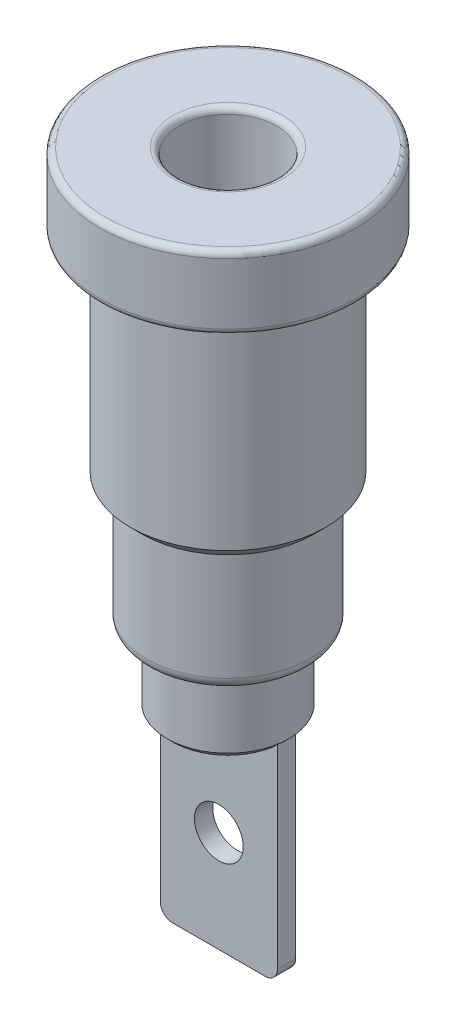
SolidWorks part; units mm, degrees
ref_plane "Front Plane" through (0, 0, 0) normal (0, 0, 1) x (1, 0, 0)
ref_plane "Top Plane" through (0, 0, 0) normal (0, 1, 0) x (1, 0, 0)
ref_plane "Right Plane" through (0, 0, 0) normal (1, 0, 0) x (0, 0, -1)
sketch "Sketch1" plane through (0, 0, 0) normal (0, 0, 1) x (1, 0, 0)
  line L0 (-2, 0) -> (-5.25, 0)
  line L1 (-5.25, 0) -> (-5.25, -3)
  line L2 (-5.25, -3) -> (-4, -3)
  line L5 (-4, -3) -> (-4, -12)
  line L6 (-4, -12) -> (-3.34, -12)
  line L7 (-3.34, -12) -> (-3.34, -16.5)
  line L8 (-2.84, -17) -> (-2.5, -17)
  line L9 (-2.5, -17) -> (-2.5, -20)
  line L10 (-2.5, -20) -> (0, -20)
  line L11 (0, -20) -> (0, -8)
  line L12 (0, -8) -> (-2, -8)
  line L13 (-2, -8) -> (-2, 0)
  line L14 (0, -8) -> (0, 0) construction
  line L15 (0, -20) -> (0, -28.3) construction
  arc A0 (-3.34, -16.5) -> (-2.84, -17) centre (-2.84, -16.5) ccw
  point P5 (-4, -13.2835)
  point P6 (0, 0)
  point P12 (0, 0)
  dimension "D1" = 8
  dimension "D11" = 0.5
  dimension "D2" = 4
  dimension "D3" = 10.5
  dimension "D4" = 3
  dimension "D5" = 5
  dimension "D6" = 8
  dimension "D7" = 11.3
  dimension "D8" = 28.3
  dimension "D9" = 5
  dimension "D10" = 6.68
  dimension "D12" = 3
revolve "Revolve1" add sketch "Sketch1" angle 360 about L15
sketch "Sketch2" plane through (0, 0, 0) normal (0, 0, 1) x (1, 0, 0)
  line L0 (-2.4, -20) -> (-2.4, -27.8)
  line L1 (-2.5, -20) -> (2.5, -20) construction
  line L2 (-1.9, -28.3) -> (1.9, -28.3)
  line L3 (2.4, -27.8) -> (2.4, -20)
  line L4 (2.4, -20) -> (-2.4, -20)
  line L5 (0, -20) -> (0, 0) construction
  line L6 (0, -20) -> (0, -28.3) construction
  arc A0 (-2.4, -27.8) -> (-1.9, -28.3) centre (-1.9, -27.8) ccw
  arc A1 (1.9, -28.3) -> (2.4, -27.8) centre (1.9, -27.8) ccw
  circle A2 centre (0, -24.15) radius 1
  dimension "D1" = 4.8
  dimension "D2" = 0.5
  dimension "D3" = 2
extrude "Boss-Extrude1" add sketch "Sketch2" along normal mid plane 0.75
chamfer "Chamfer1" distance 0.25 angle 45 1 edges at (-2.5, -20, 0)
chamfer "Chamfer2" distance 0.5 angle 45 1 edges at (-4, -12, 0)
fillet "Fillet1" radius 0.25 4 edges at (-2, -8, 0) (-2, 0, 0) (-5.25, 0, 0) (-5.25, -3, 0)
